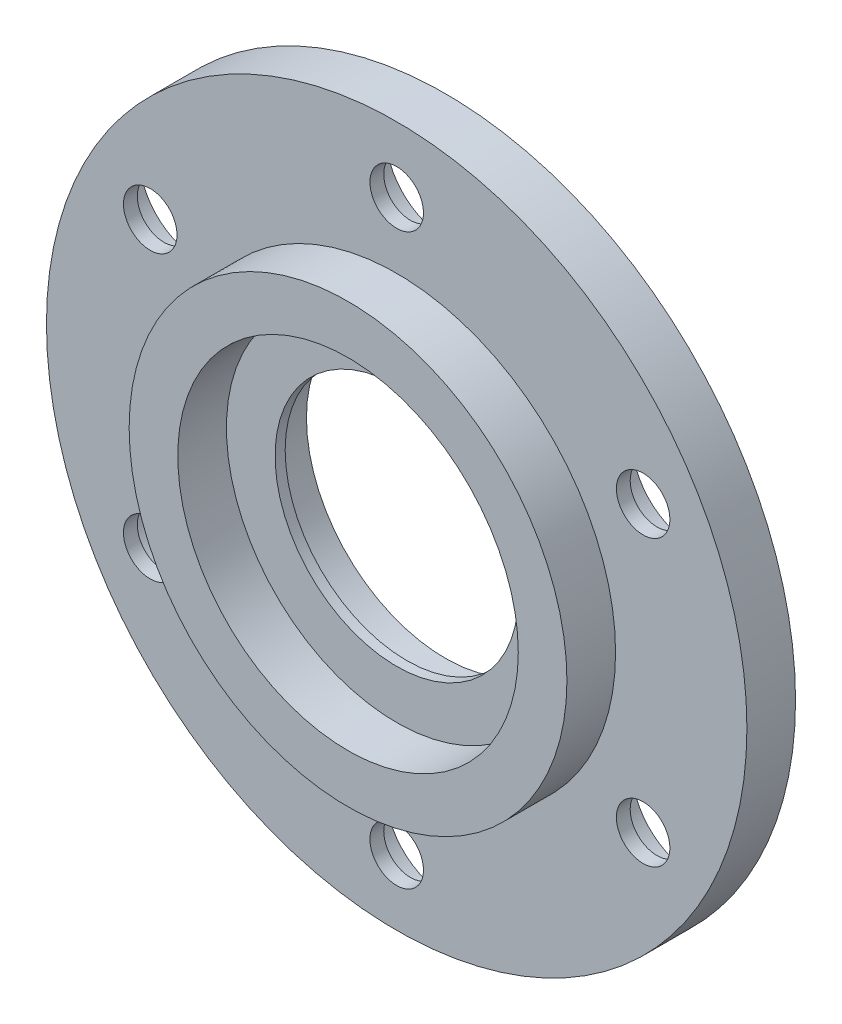
SolidWorks part; units mm, degrees
material "6061-T6 (SS)"
ref_plane "Front Plane" through (0, 0, 0) normal (0, 0, 1) x (1, 0, 0)
ref_plane "Top Plane" through (0, 0, 0) normal (0, 1, 0) x (1, 0, 0)
ref_plane "Right Plane" through (0, 0, 0) normal (1, 0, 0) x (0, 0, -1)
sketch "Sketch Spindle Skeleton" plane through (0, 0, 0) normal (1, 0, 0) x (0, 0, -1)
  line L0 (-109.9, -9.5) -> (-139, -9.5)
  line L5 (-1000, 0) -> (49000, 0)
  line L6 (0, -9.5) -> (0, 9.5)
  line L13 (0, 9.5) -> (-48.3, 9.5)
  line L26 (-48.3, 9.5) -> (-48.3, 14)
  line L27 (-48.3, 14) -> (-109.9, 14)
  line L32 (-109.9, 14) -> (-109.9, 9.5)
  line L34 (-155, 7) -> (-155, -7)
  line L36 (-109.9, -9.5) -> (-109.9, -14)
  line L37 (-109.9, -14) -> (-48.3, -14)
  line L38 (-48.3, -14) -> (-48.3, -9.5)
  line L39 (0, -9.5) -> (-48.3, -9.5)
  line L40 (-20.2, 36) -> (-15.2, 36)
  line L41 (-126.5, 22.5) -> (-109.9, 22.5)
  line L42 (-126.5, 22.5) -> (-126.5, -22.5)
  line L43 (-126.5, -22.5) -> (-109.9, -22.5)
  line L44 (-109.9, 22.5) -> (-109.9, -22.5)
  line L45 (-126.5, 22.5) -> (-109.9, -22.5) construction
  line L46 (-126.5, -22.5) -> (-109.9, 22.5) construction
  line L47 (-31.7, 22.5) -> (-48.3, 22.5)
  line L48 (-31.7, 22.5) -> (-31.7, -22.5)
  line L49 (-31.7, -22.5) -> (-48.3, -22.5)
  line L50 (-48.3, 22.5) -> (-48.3, -22.5)
  line L51 (-31.7, 22.5) -> (-48.3, -22.5) construction
  line L52 (-31.7, -22.5) -> (-48.3, 22.5) construction
  line L59 (-15.2, 36) -> (-15.2, -36)
  line L60 (-15.2, -36) -> (-20.2, -36)
  line L61 (-20.2, -22.5) -> (-25.2, -22.5)
  line L62 (-25.2, -22.5) -> (-25.2, -17.5)
  line L63 (-25.2, -17.5) -> (-20.2, -17.5)
  line L64 (-20.2, -17.5) -> (-20.2, 17.5)
  line L65 (-20.2, 17.5) -> (-25.2, 17.5)
  line L66 (-25.2, 17.5) -> (-25.2, 22.5)
  line L67 (-25.2, 22.5) -> (-20.2, 22.5)
  line L68 (-20.2, 22.5) -> (-20.2, 36)
  line L69 (-20.2, -22.5) -> (-20.2, -36)
  line L71 (-131.5, 36) -> (-21.2, 36)
  line L72 (-131.5, 36) -> (-131.5, -36)
  line L73 (-131.5, -36) -> (-21.2, -36)
  line L74 (-21.2, 36) -> (-21.2, -36)
  line L75 (-131.5, 36) -> (-21.2, -36) construction
  line L76 (-131.5, -36) -> (-21.2, 36) construction
  line L77 (-139, -9.5) -> (-139, -7)
  line L78 (-139, -7) -> (-155, -7)
  line L79 (-109.9, 9.5) -> (-139, 9.5)
  line L80 (-139, 7) -> (-155, 7)
  line L81 (-139, 9.5) -> (-139, 7)
  line L82 (-124.45, 9.5) -> (-124.45, -9.5) construction
  line L83 (-24.15, 9.5) -> (-24.15, -9.5) construction
  line L96 (-131.5, 36) -> (-136.5, 36)
  line L97 (-131.5, 36) -> (-131.5, 22.5)
  line L98 (-131.5, -36) -> (-136.5, -36)
  line L99 (-136.5, 36) -> (-136.5, -36)
  line L100 (-131.5, 17.5) -> (-126.5, 17.5)
  line L102 (-131.5, 22.5) -> (-126.5, 22.5)
  line L103 (-126.5, 17.5) -> (-126.5, 22.5)
  line L104 (-131.5, -22.5) -> (-126.5, -22.5)
  line L106 (-131.5, -17.5) -> (-126.5, -17.5)
  line L107 (-126.5, -22.5) -> (-126.5, -17.5)
  line L108 (-131.5, -22.5) -> (-131.5, -36)
  line L109 (-131.5, 17.5) -> (-131.5, -17.5)
  point P3 (0, 0)
  point P18 (-118.2, 0)
  point P24 (-40, 0)
  point P29 (-76.35, 0)
  point P48 (-15.2, 29.25)
  point P70 (-136.5, 29.25)
revolve "Main Revolve" add sketch "Sketch Spindle Skeleton" angle 360 about L5 region at (0, 22.65, 17.8091) region at (0, 20, 23.2)
sketch "Sketch Center Cut" plane through (0, 0, 20.2) normal (0, 0, 1) x (1, 0, 0)
  circle A0 centre (0, 0) radius 17.5 construction
  circle A1 centre (0, 0) radius 17.5 construction
  circle A2 centre (0, 0) radius 12.5
  dimension "D1" = 5
extrude "Cut Center" cut sketch "Sketch Center Cut" against normal through all
hole_wizard "CBORE for M5 Hex Head Bolt1" positions "Hole wizard sketch 1" profile "Hole wizard sketch 2" counterbore size "M5" standard "ANSI Metric" end condition through all
sketch "Hole wizard sketch 1" plane through (0, 0, 15.2) normal (0, 0, -1) x (-1, 0, 0)
  point P0 (0, 29.25)
sketch "Hole wizard sketch 2" plane through (0, 29.25, 15.2) normal (1, 0, 0) x (0, 1, 0)
  line L0 (0, 0) -> (0, 10)
  line L1 (0, 10) -> (2.75, 10)
  line L3 (2.75, 10) -> (2.75, 3.58)
  line L4 (2.75, 3.58) -> (6.12, 3.58)
  line L5 (6.12, 3.58) -> (6.12, 0)
  line L7 (6.12, 0) -> (0, 0)
  line L11 (0, -6.35) -> (0, 107.95) construction
  dimension "Thru Hole Dia." = 5.5
  dimension "Thru Hole Depth" = 10
  dimension "C'Bore Dia." = 12.24
  dimension "C'Bore Depth" = 3.58
pattern_circular "CirPattern1" count 6 over 360 about axis through (0, 0, 15.2) along (0, 0, 1) of "CBORE for M5 Hex Head Bolt1"
sketch "Sketch1" plane through (0, 0, 15.2) normal (0, 0, -1) x (-1, 0, 0)
  circle A0 centre (0, 0) radius 14.2748
  dimension "D1" = 28.5496
extrude "Cut-Extrude1" cut sketch "Sketch1" against normal blind 3.9624
